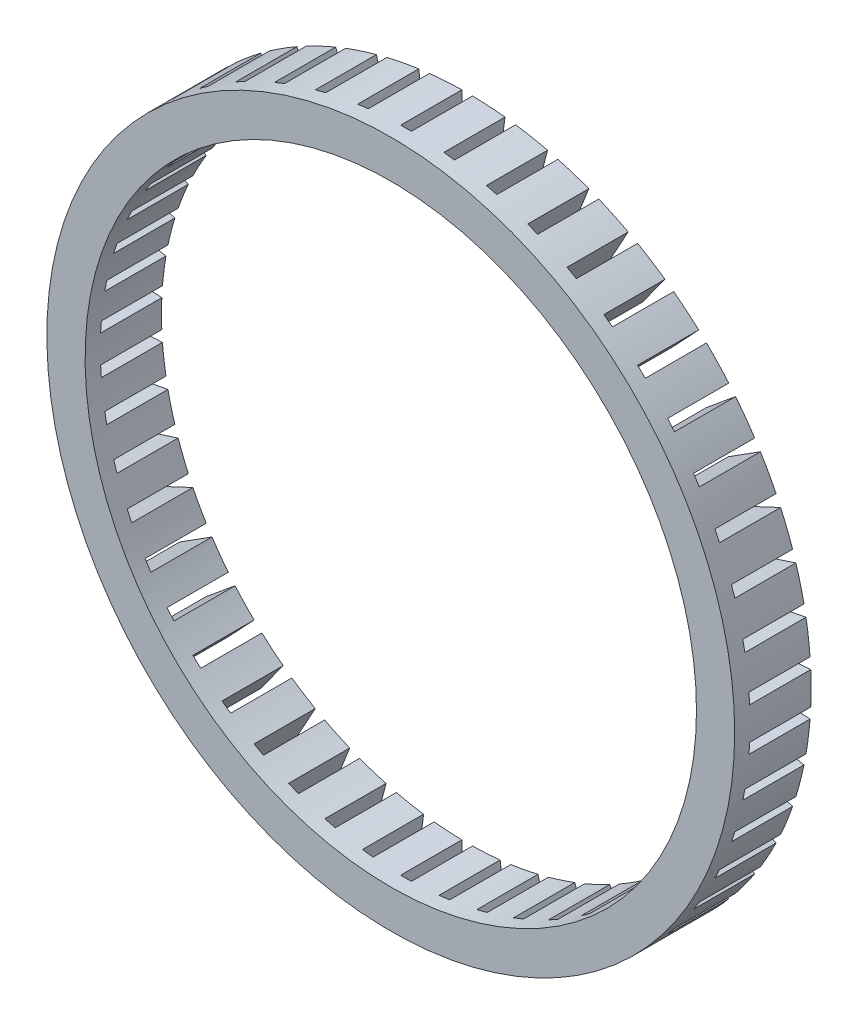
SolidWorks part; units mm, degrees
ref_plane "Front Plane" through (0, 0, 0) normal (0, 0, 1) x (1, 0, 0)
ref_plane "Top Plane" through (0, 0, 0) normal (0, 1, 0) x (1, 0, 0)
ref_plane "Right Plane" through (0, 0, 0) normal (1, 0, 0) x (0, 0, -1)
sketch "Sketch1" plane through (0, 0, 0) normal (0, 0, 1) x (1, 0, 0)
  circle A0 centre (0, 0) radius 40
  circle A1 centre (0, 0) radius 45
  dimension "D1" = 80
  dimension "D2" = 90
extrude "Boss-Extrude1" add sketch "Sketch1" along normal blind 10 contours A1 | A0
sketch "Sketch2" plane through (0, 0, 10) normal (0, 0, 1) x (1, 0, 0)
  line L0 (0, 0) -> (0, 45)
  circle A1 centre (0, 0) radius 45 construction
sketch "Sketch3" plane through (0, 0, 0) normal (0, 1, 0) x (1, 0, 0)
  line L0 (-0.7, 0) -> (-0.7, -8)
  line L1 (-0.7, -8) -> (0.7, -8)
  line L2 (0.7, -8) -> (0.7, 0)
  line L3 (0.7, 0) -> (-0.7, 0)
  point P2 (0, 0)
  dimension "D1" = 8
  dimension "D2" = 1.4
extrude "Cut-Extrude1" cut sketch "Sketch3" against normal through all both and the other way through all
ref_axis "Axis2" through (0, 0, -0.5) along (0, 0, 1)
pattern_circular "CirPattern1" count 50 over 360 about axis through (0, 0, -0.5) along (0, 0, 1) of "Cut-Extrude1"
